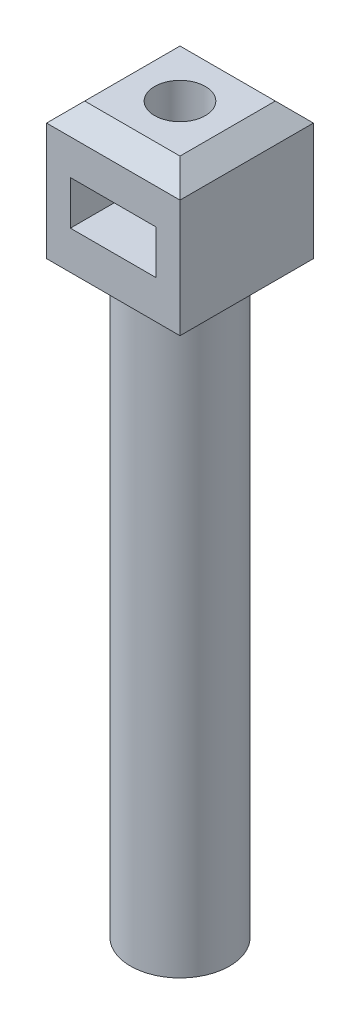
SolidWorks part; units mm, degrees
ref_plane "Front Plane" through (0, 0, 0) normal (0, 0, 1) x (1, 0, 0)
ref_plane "Top Plane" through (0, 0, 0) normal (0, 1, 0) x (1, 0, 0)
ref_plane "Right Plane" through (0, 0, 0) normal (1, 0, 0) x (0, 0, -1)
sketch "Sketch1" plane through (0, 0, 0) normal (0, 1, 0) x (1, 0, 0)
  circle A0 centre (0, 0) radius 6.604
  dimension "D1" = 13.208
extrude "Boss-Extrude1" add sketch "Sketch1" along normal blind 63.5
sketch "Sketch4" plane through (0, 0, 0) normal (0, -1, 0) x (1, 0, 0)
  line L1 (-12.7, -12.7) -> (12.7, -12.7)
  line L2 (-12.7, -12.7) -> (-12.7, 12.7)
  line L3 (-12.7, 12.7) -> (12.7, 12.7)
  line L4 (12.7, -12.7) -> (12.7, 12.7)
  line L5 (-12.7, -12.7) -> (12.7, 12.7) construction
  line L6 (-12.7, 12.7) -> (12.7, -12.7) construction
  point P0 (0, 0)
  dimension "D1" = 25.4
  dimension "D2" = 25.4
extrude "Boss-Extrude2" add sketch "Sketch4" along normal blind 1.27
ref_axis "Axis2" through (0, 63.5, 0) along (0, -1, 0)
ref_plane "Plane2" through (0, 50.8, 0) normal (0, 1, 0) x (1, 0, 0)
sketch "Sketch9" plane through (0, 50.8, 0) normal (0, 1, 0) x (1, 0, 0)
  line L1 (-8.89, -8.89) -> (8.89, -8.89)
  line L2 (-8.89, -8.89) -> (-8.89, 8.89)
  line L3 (-8.89, 8.89) -> (8.89, 8.89)
  line L4 (8.89, -8.89) -> (8.89, 8.89)
  line L5 (-8.89, -8.89) -> (8.89, 8.89) construction
  line L6 (-8.89, 8.89) -> (8.89, -8.89) construction
  point P0 (0, 0)
  dimension "D1" = 17.78
  dimension "D2" = 17.78
extrude "Boss-Extrude4" add sketch "Sketch9" along normal blind 20.32
sketch "Sketch10" plane through (0, 0, 8.89) normal (0, 0, 1) x (1, 0, 0)
  line L0 (0, 63.5) -> (0, 0) construction
  line L1 (-5.715, 58.039) -> (5.715, 58.039)
  line L2 (-5.715, 58.039) -> (-5.715, 63.881)
  line L3 (-5.715, 63.881) -> (5.715, 63.881)
  line L4 (5.715, 58.039) -> (5.715, 63.881)
  line L5 (-5.715, 58.039) -> (5.715, 63.881) construction
  line L6 (-5.715, 63.881) -> (5.715, 58.039) construction
  line L7 (-8.89, 71.12) -> (8.89, 71.12) construction
  line L8 (-8.89, 50.8) -> (8.89, 50.8) construction
  point P0 (0, 60.96)
  dimension "D1" = 11.43
  dimension "D2" = 5.842
  dimension "D3" = 7.239
  dimension "D4" = 7.239
extrude "Cut-Extrude2" cut sketch "Sketch10" against normal through all both and the other way through all
chamfer "Chamfer2" distance 2.54 angle 40 4 edges at (0, 50.8, -8.89) (-8.89, 50.8, 0) (8.89, 50.8, 0) (0, 50.8, 8.89) first distance on face at (0, 50.8, 0)
sketch "Sketch13" plane through (0, -1.27, 0) normal (0, -1, 0) x (1, 0, 0)
  line L1 (-12.7, 12.7) -> (12.7, 12.7)
  line L2 (-12.7, 12.7) -> (-12.7, -12.7)
  line L3 (-12.7, -12.7) -> (12.7, -12.7)
  line L4 (12.7, 12.7) -> (12.7, -12.7)
extrude "Cut-Extrude3" cut sketch "Sketch13" against normal blind 1.27
hole_wizard "1/4 Clearance Hole1" positions "Sketch16" profile "Sketch15" hole size "1/4" standard "ANSI Inch" end condition up to next
sketch "Sketch16" plane through (0, 71.12, 0) normal (0, 1, 0) x (1, 0, 0)
  point P0 (0, 0)
sketch "Sketch15" plane through (0, 71.12, 0) normal (1, 0, 0) x (0, 0, 1)
  line L0 (0, 0) -> (0, 7.239)
  line L1 (0, 7.239) -> (3.3782, 7.239)
  line L2 (3.3782, 7.239) -> (3.3782, 0)
  line L5 (3.3782, 0) -> (0, 0)
  line L11 (0, -6.35) -> (0, 107.95) construction
  dimension "Thru Hole Dia." = 6.7564
  dimension "Thru Hole Depth" = 7.239
chamfer "Chamfer3" distance 2.54 angle 45 1 edges at (8.89, 71.12, 0)
chamfer "Chamfer4" distance 2.54 angle 45 3 edges at (-1.27, 71.12, -8.89) (-8.89, 71.12, 0) (-1.27, 71.12, 8.89)
sketch "Sketch17" plane through (0, 0, 0) normal (0, -1, 0) x (1, 0, 0)
  circle A0 centre (0, 0) radius 6.604
extrude "Boss-Extrude5" add sketch "Sketch17" along normal blind 25.4
